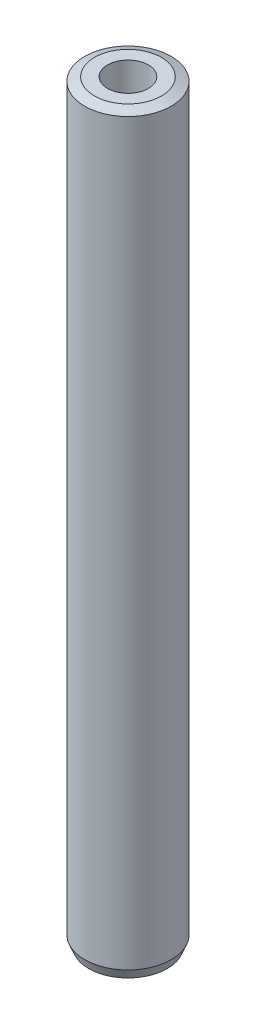
SolidWorks part; units mm, degrees
ref_plane "Front Plane" through (0, 0, 0) normal (0, 0, 1) x (1, 0, 0)
ref_plane "Top Plane" through (0, 0, 0) normal (0, 1, 0) x (1, 0, 0)
ref_plane "Right Plane" through (0, 0, 0) normal (1, 0, 0) x (0, 0, -1)
sketch "Sketch1" plane through (0, 0, 0) normal (0, 1, 0) x (1, 0, 0)
  circle A0 centre (0, 0) radius 12.5
  dimension "SHAFT_OD" = 25
extrude "Boss-Extrude1" add sketch "Sketch1" along normal blind 217.7349
sketch "Sketch2" plane through (0, 0, 0) normal (0, 1, 0) x (1, 0, 0)
  circle A0 centre (0, 0) radius 5.9037
  dimension "BORE_D" = 11.8073
extrude "Cut-Extrude1" cut sketch "Sketch2" along normal through all
chamfer "Chamfer1" distance 1.1537 angle 67.743 2 edges at (0, 217.7349, 12.5) (0, 0, 12.5) first distance on face at (0, 217.7349, 12.5) first distance on face at (0, 0, 5.9037)
